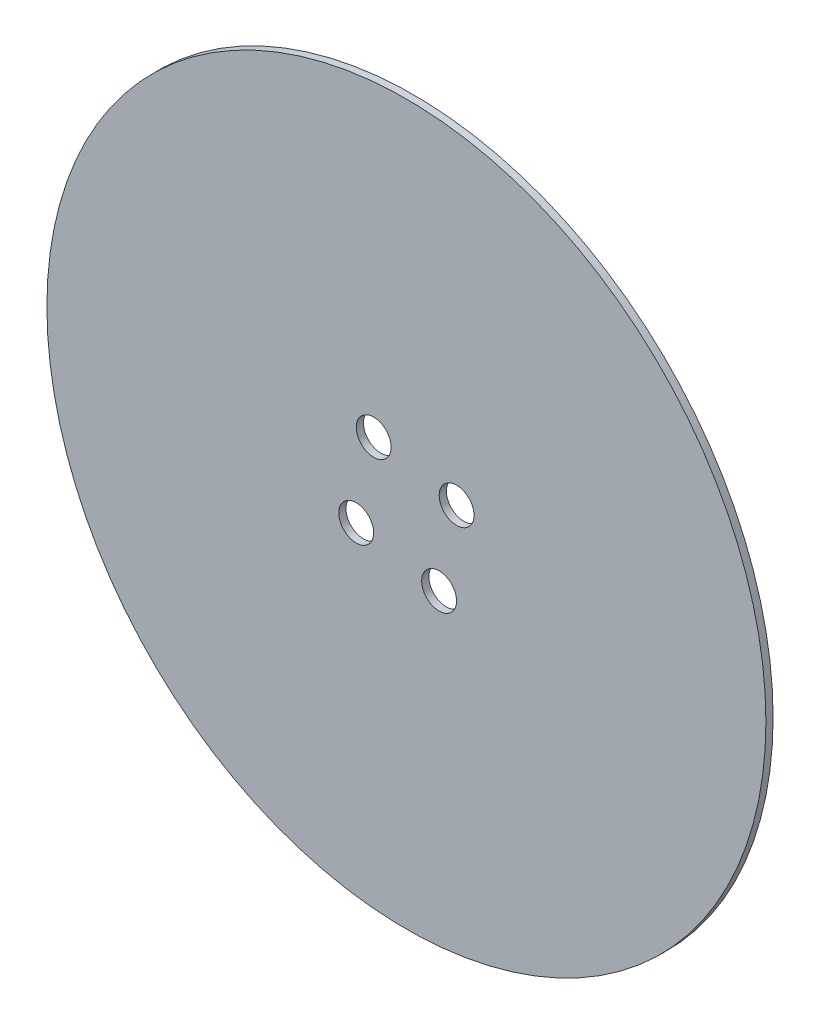
SolidWorks part; units mm, degrees
ref_plane "Front Plane" through (0, 0, 0) normal (0, 0, 1) x (1, 0, 0)
ref_plane "Top Plane" through (0, 0, 0) normal (0, 1, 0) x (1, 0, 0)
ref_plane "Right Plane" through (0, 0, 0) normal (1, 0, 0) x (0, 0, -1)
sketch "Sketch1" plane through (0, 0, 0) normal (0, 0, 1) x (1, 0, 0)
  line L0 (0, 0) -> (0, 140) construction
  line L1 (0, 140) -> (0, 150) construction
  line L2 (-12.5, 140) -> (12.5, 140) construction
  circle A0 centre (0, 0) radius 150
  point P9 (0, 140)
  point P21 (0, 0)
  dimension "D1" = 300
  dimension "D5" = 140
extrude "Boss-Extrude2" add sketch "Sketch1" along normal blind 3
sketch "Sketch2" plane through (0, 0, 0) normal (0, 0, -1) x (-1, 0, 0)
  circle A13 centre (-13.6439, -20.9486) radius 3.2 construction
  circle A14 centre (20.9486, -13.6439) radius 3.2 construction
  circle A15 centre (13.6439, 20.9486) radius 3.2 construction
  circle A16 centre (-20.9486, 13.6439) radius 3.2 construction
  circle A17 centre (-13.6439, -20.9486) radius 3.2
  circle A18 centre (20.9486, -13.6439) radius 3.2
  circle A19 centre (13.6439, 20.9486) radius 3.2
  circle A20 centre (-20.9486, 13.6439) radius 3.2
hole_wizard "CBORE for M6 Hex Head Bolt1" positions "Sketch8" profile "Sketch9" counterbore size "M6" standard "ANSI Metric" end condition through all
sketch "Sketch8" plane through (0, 0, 0) normal (0, 0, -1) x (-1, 0, 0)
  point P0 (-20.9486, 13.6439)
  point P3 (13.6439, 20.9486)
  point P6 (20.9486, -13.6439)
  point P9 (-13.6439, -20.9486)
sketch "Sketch9" plane through (20.9486, 13.6439, 0) normal (1, 0, 0) x (0, 1, 0)
  line L0 (0, 0) -> (0, 3)
  line L1 (0, 3) -> (3.3, 3)
  line L3 (3.3, 3) -> (3.3, 4.38)
  line L4 (3.3, 4.38) -> (7.275, 4.38)
  line L5 (7.275, 4.38) -> (7.275, 0)
  line L7 (7.275, 0) -> (0, 0)
  line L11 (0, -6.35) -> (0, 107.95) construction
  dimension "Thru Hole Dia." = 6.6
  dimension "Thru Hole Depth" = 3
  dimension "C'Bore Dia." = 14.55
  dimension "C'Bore Depth" = 4.38
